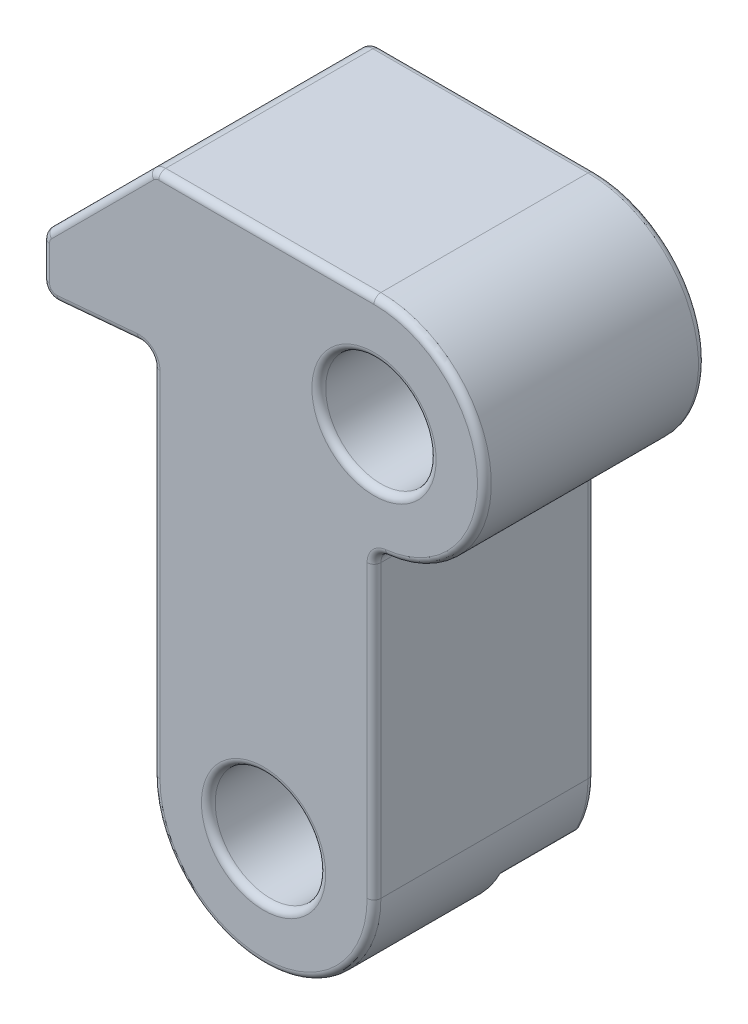
SolidWorks part; units mm, degrees
ref_plane "Front Plane" through (0, 0, 0) normal (0, 0, 1) x (1, 0, 0)
ref_plane "Top Plane" through (0, 0, 0) normal (0, 1, 0) x (1, 0, 0)
ref_plane "Right Plane" through (0, 0, 0) normal (1, 0, 0) x (0, 0, -1)
sketch "Sketch1" plane through (0, 0, 0) normal (0, 0, 1) x (1, 0, 0)
  line L0 (6.35, 0) -> (6.35, 16.713)
  line L1 (6.35, 30.1625) -> (-6.0212, 30.1625)
  line L2 (-6.5825, 29.93) -> (-12.4675, 24.045)
  line L3 (-12.7, 23.4837) -> (-12.7, 21.5037)
  line L4 (-11.8371, 20.713) -> (-7.2129, 21.1176)
  line L5 (-6.35, 20.3268) -> (-6.35, 0)
  line L6 (-12.7, 20.6375) -> (-12.7, 30.1625) construction
  arc A0 (-6.35, 0) -> (6.35, 0) centre (0, 0) ccw
  arc A1 (7.0556, 17.5018) -> (6.35, 30.1625) centre (6.35, 23.8125) ccw
  circle A2 centre (0, 0) radius 3.175
  circle A3 centre (6.35, 23.8125) radius 3.175
  arc A4 (-7.2129, 21.1176) -> (-6.35, 20.3268) centre (-7.1438, 20.3268) cw
  arc A5 (6.35, 16.713) -> (7.0556, 17.5018) centre (7.1438, 16.713) cw
  arc A6 (-6.0212, 30.1625) -> (-6.5825, 29.93) centre (-6.0212, 29.3688) ccw
  arc A7 (-12.4675, 24.045) -> (-12.7, 23.4837) centre (-11.9063, 23.4837) ccw
  arc A8 (-12.7, 21.5037) -> (-11.8371, 20.713) centre (-11.9063, 21.5037) ccw
  point P4 (-12.7, 25.4)
  point P16 (-12.7, 22.4937)
  point P20 (6.35, 17.4625)
  point P23 (-6.35, 30.1625)
  point P26 (-12.7, 23.8125)
  dimension "D1" = 6.35
  dimension "D2" = 6.35
  dimension "D3" = 6.35
  dimension "D4" = 6.35
  dimension "D11" = 0.7937
  dimension "D5" = 9.525
  dimension "D6" = 85
  dimension "D7" = 6.35
  dimension "D8" = 25.4
  dimension "D9" = 6.35
  dimension "D10" = 6.35
extrude "Boss-Extrude1" add sketch "Sketch1" against normal blind 12.7
sketch "Sketch2" plane through (0, 0, -12.7) normal (0, 0, -1) x (-1, 0, 0)
  line L9 (0, 36.1558) -> (0, -16.7836) construction
  line L10 (3.9687, 26.1705) -> (3.9687, 6.7352)
  line L11 (4.7625, 26.1705) -> (3.9687, 26.1705)
  line L12 (4.7625, 3.2727) -> (4.7625, 26.1705)
  line L13 (-20.3049, -4.7625) -> (-6.3994, -4.7625)
  line L14 (-20.3049, -5.5562) -> (-20.3049, -4.7625)
  line L15 (0, -5.5562) -> (-20.3049, -5.5562)
  arc A6 (1.8521, 5.2385) -> (3.9687, 6.7352) centre (2.3812, 6.7352) ccw
  arc A7 (4.7625, 3.2727) -> (4.9389, 2.5454) centre (6.35, 3.2727) ccw
  arc A8 (-6.3994, -4.7625) -> (-4.9773, -2.4694) centre (-6.3994, -3.175) ccw
  arc A9 (-4.9773, -2.4694) -> (1.8521, 5.2385) centre (0, 0) cw
  arc A10 (4.9389, 2.5454) -> (0, -5.5562) centre (0, 0) cw
  point P45 (-2.8619, -4.7625)
  point P46 (5.5563, 0)
extrude "Cut-Extrude1" cut sketch "Sketch2" against normal blind 4.7625
fillet "Fillet2" radius 0.3969 2 edges at (3.0742, -5.5562, -10.3187) (4.9968, -3.9185, -10.3187)
fillet "Fillet3" radius 0.3969 40 edges at (3.175, 0, 0) (9.525, 23.8125, 0) (0.1644, 30.1625, 0) (-6.325, 30.1021, 0) (-9.525, 26.9875, 0) (-12.6396, 23.7875, 0) (-12.7, 22.4937, 0) (-12.4425, 20.9185, 0) (-9.525, 20.9153, 0) (-6.6075, 20.912, 0) (-6.35, 10.1634, 0) (0, -6.35, 0) (6.35, 8.3565, 0) (6.5521, 17.2422, 0) (12.6902, 24.1658, 0) (9.525, 23.8125, -12.7) (-6.35, 10.1634, -12.7) (-6.6075, 20.912, -12.7) (-9.525, 20.9153, -12.7) (-12.4425, 20.9185, -12.7) (-12.7, 22.4937, -12.7) (-12.6396, 23.7875, -12.7) (-9.525, 26.9875, -12.7) (-6.325, 30.1021, -12.7) (0.1644, 30.1625, -12.7) (12.6902, 24.1658, -12.7) (6.5521, 17.2422, -12.7) (6.35, 8.3565, -12.7) (3.175, 0, -7.9375) (-4.8072, 2.8985, -12.7) (-4.7625, 14.7216, -12.7) (-4.3656, 26.1705, -12.7) (-3.9687, 16.4528, -12.7) (-3.2978, 5.439, -12.7) (4.1587, 3.6847, -12.7) (6.1824, -1.4494, -12.7) (-4.4901, -4.4901, -12.7) (-4.7442, -2.8921, -12.7) (5.1565, -3.0014, -12.7) (0.3969, -5.9531, -12.7)
